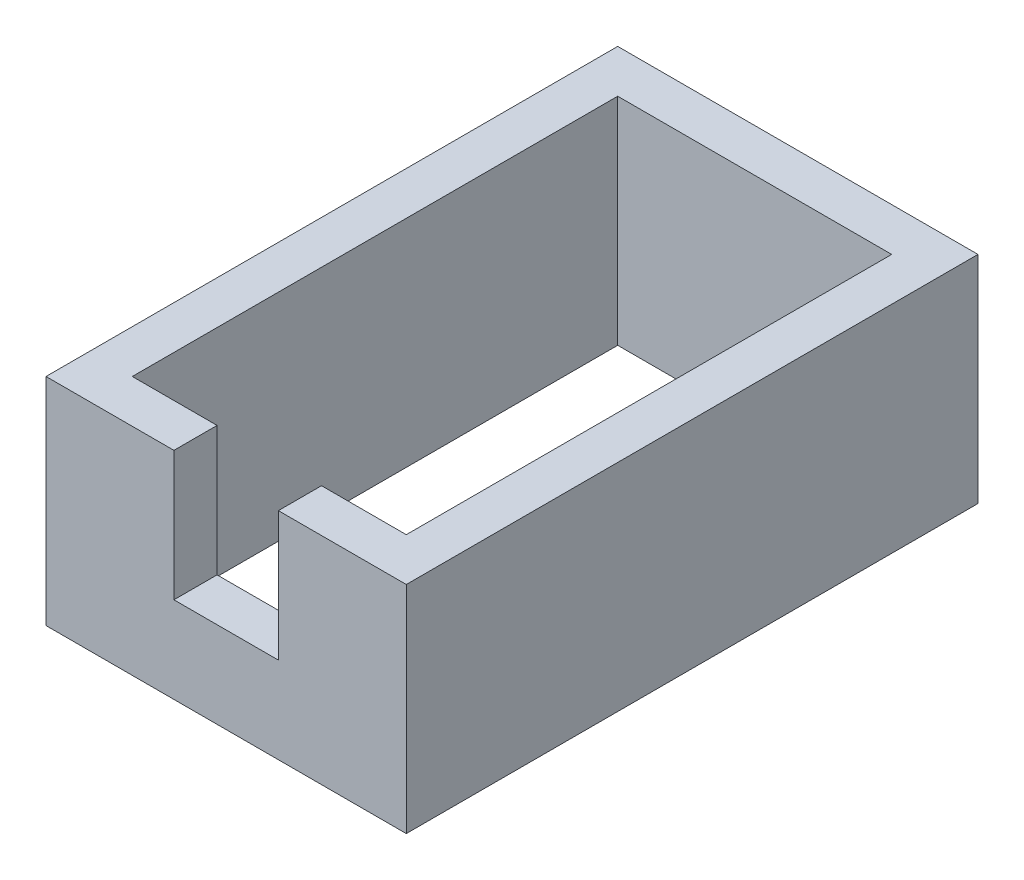
SolidWorks part; units mm, degrees
ref_plane "Front Plane" through (0, 0, 0) normal (0, 0, 1) x (1, 0, 0)
ref_plane "Top Plane" through (0, 0, 0) normal (0, 1, 0) x (1, 0, 0)
ref_plane "Right Plane" through (0, 0, 0) normal (1, 0, 0) x (0, 0, -1)
sketch "Sketch1" plane through (0, 0, 0) normal (0, 1, 0) x (1, 0, 0)
  line L0 (0, 0) -> (0, -2) construction
  line L1 (0, 0) -> (12.7, 0)
  line L2 (0, 0) -> (0, 22.5)
  line L3 (0, 22.5) -> (12.7, 22.5)
  line L4 (12.7, 0) -> (12.7, 22.5)
  line L5 (0, -2) -> (-2, -2) construction
  line L6 (12.7, 22.5) -> (14.7, 22.5) construction
  line L7 (14.7, 22.5) -> (14.7, 24.5) construction
  line L8 (6.35, -2) -> (6.35, 0) construction
  line L9 (-2, -2) -> (14.7, -2)
  line L10 (-2, -2) -> (-2, 24.5)
  line L11 (-2, 24.5) -> (14.7, 24.5)
  line L12 (14.7, -2) -> (14.7, 24.5)
  line L13 (8.7708, 0) -> (8.7708, -2)
  line L14 (3.9292, 0) -> (3.9292, -2)
  dimension "D1" = 22.5
  dimension "D2" = 12.7
  dimension "D3" = 2
  dimension "D4" = 2
  dimension "D5" = 2
  dimension "D6" = 2
extrude "Boss-Extrude1" add sketch "Sketch1" along normal blind 10 contours L14 L1 L2 L3 L4 L13 L9 L12 L11 L10 region at (1.9646, 0, 0.3132)
extrude "Boss-Extrude2" add sketch "Sketch1<3>" along normal blind 4 contours L1 L14 L9 L13 region at (6.35, 0, 1)
sketch "Sketch1<3>" plane through (0, 0, 0) normal (0, 1, 0) x (1, 0, 0) same geometry as "Sketch1"
